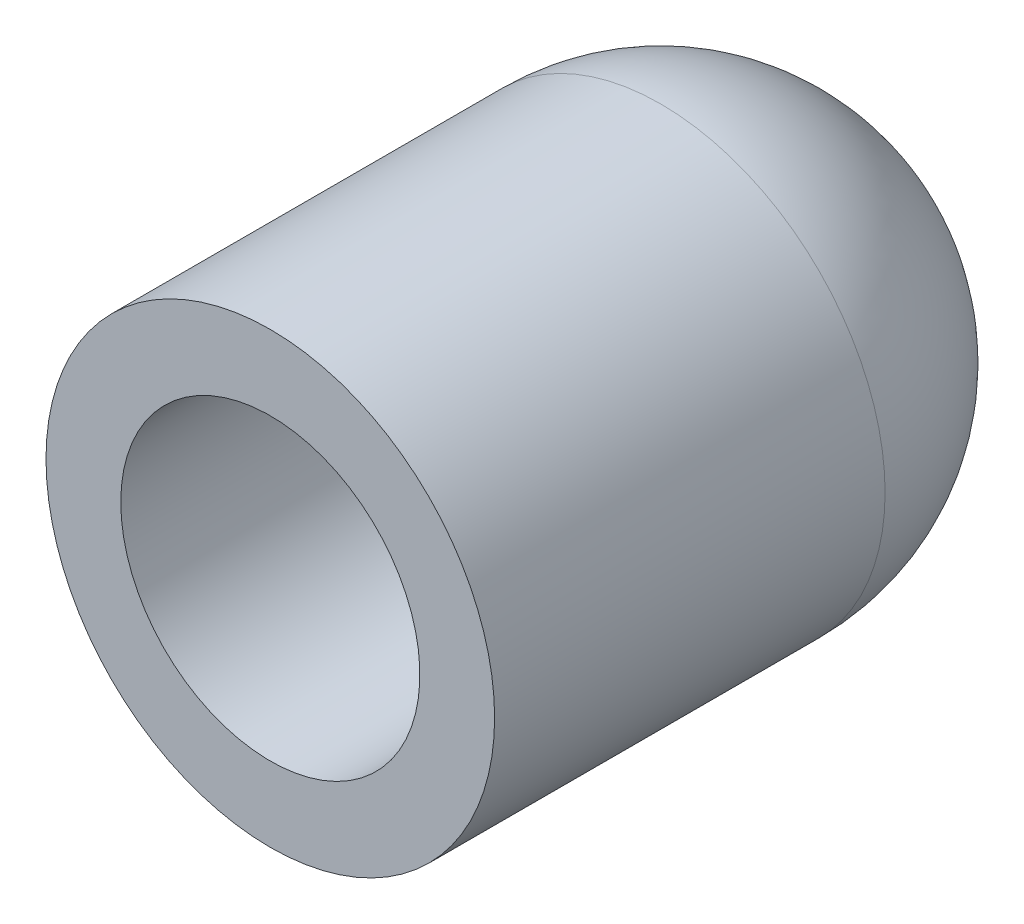
SolidWorks part; units mm, degrees
ref_plane "Front" through (0, 0, 0) normal (0, 0, 1) x (1, 0, 0)
ref_plane "Top" through (0, 0, 0) normal (0, 1, 0) x (1, 0, 0)
ref_plane "Right" through (0, 0, 0) normal (1, 0, 0) x (0, 0, -1)
sketch "Sketch1" plane through (0, 0, 0) normal (0, 1, 0) x (1, 0, 0)
  line L0 (0, 3.375) -> (0, -5.875)
  line L1 (3.375, 0) -> (-3.375, 0)
  line L2 (3.375, 0) -> (3.375, -5.875)
  line L3 (3.375, -5.875) -> (-3.375, -5.875)
  line L4 (-3.375, 0) -> (-3.375, -5.875)
  line L5 (2.25, 0) -> (2.25, -5.875)
  line L6 (2.25, -4.75) -> (-2.25, -4.75)
  line L7 (-2.25, 0) -> (-2.25, -4.75)
  line L8 (2.25, -1.125) -> (-2.25, -1.125)
  line L9 (2.25, -1.125) -> (2.25, -4.75) construction
  line L10 (-2.25, -1.125) -> (-2.25, -4.75) construction
  circle A0 centre (0, 0) radius 3.375
  circle A1 centre (0, 0) radius 2.25
  dimension "D1" = 6.75
  dimension "D3" = 9.25
  dimension "D2" = 1.125
revolve "Revolve1" add sketch "Sketch1" angle 360 about L0 region at (1.8144, 0, -1.8144) region at (2.7071, 0, 0.9685) region at (2.8569, 0, 3.7676)
